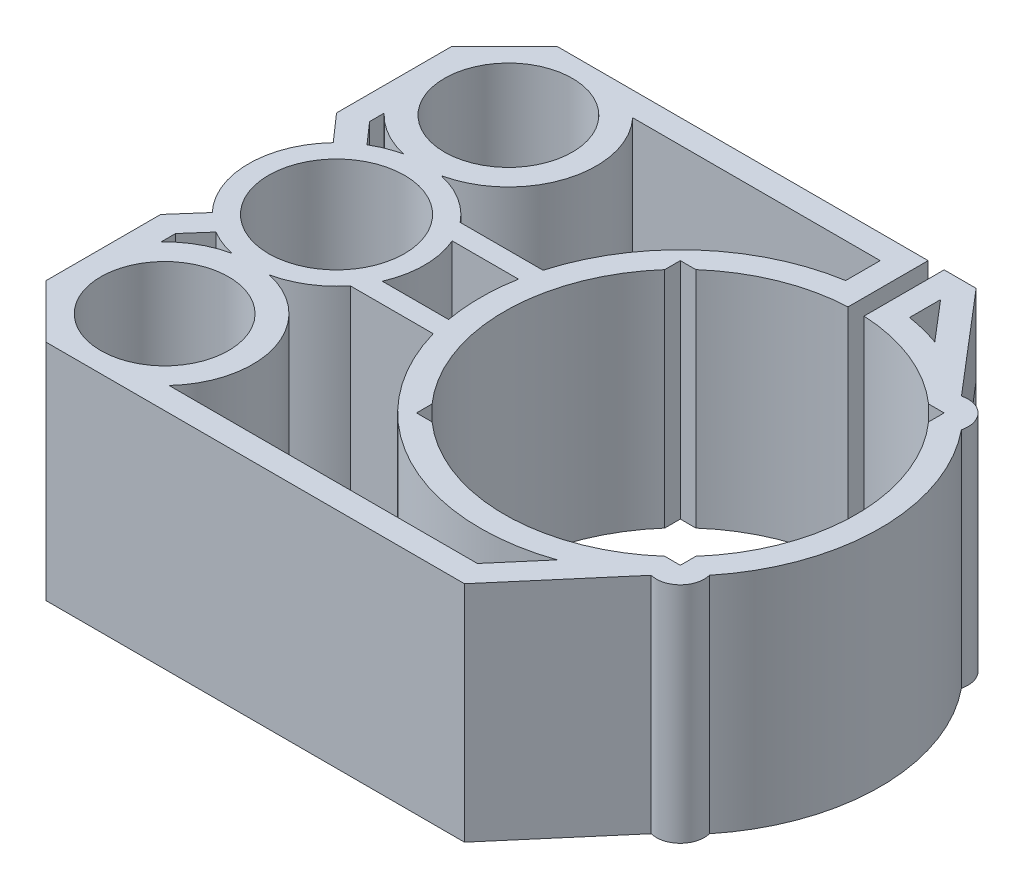
SolidWorks part; units mm, degrees
ref_plane "Front Plane" through (0, 0, 0) normal (0, 0, 1) x (1, 0, 0)
ref_plane "Top Plane" through (0, 0, 0) normal (0, 1, 0) x (1, 0, 0)
ref_plane "Right Plane" through (0, 0, 0) normal (1, 0, 0) x (0, 0, -1)
sketch "Sketch1" plane through (0, 0, 0) normal (0, 1, 0) x (1, 0, 0)
  line L0 (0, 0) -> (0, 16.5) construction
  line L1 (0, 16.5) -> (16.5, 16.5) construction
  line L2 (16.5, 16.5) -> (-16.5, -16.5) construction
  line L3 (0, 22) -> (0, 32) construction
  line L4 (16.5, 16.5) -> (-16.5, 16.5)
  line L5 (16.5, 16.5) -> (16.5, -16.5)
  line L6 (16.5, -16.5) -> (-16.5, -16.5)
  line L7 (-16.5, 16.5) -> (-16.5, -16.5)
  line L8 (1, 22) -> (1, 32)
  line L9 (-1, 22) -> (-1, 32)
  line L10 (1, 32) -> (5, 32)
  line L11 (5, 32) -> (15.7595, 19.4072)
  line L12 (18.6213, 18.6213) -> (16.5, 16.5) construction
  line L13 (4, 21.6333) -> (4, 28.5521)
  line L14 (-34.9533, 29) -> (-23.2995, 29)
  line L15 (4, 28.5521) -> (13.6619, 17.2439)
  line L16 (5, -32) -> (15.7595, -19.4072)
  line L17 (0, 0) -> (0, -25) construction
  line L18 (0, -25) -> (0, -32) construction
  line L19 (0, -32) -> (5, -32)
  line L20 (0, -32) -> (-23.2995, -32)
  line L21 (-1, 32) -> (-23.2995, 32)
  line L22 (0, -29) -> (-23.2995, -29)
  line L23 (0, -29) -> (3.6179, -29)
  line L24 (3.6179, -29) -> (13.6638, -17.2424)
  line L25 (-4, 22) -> (-4, 29)
  line L26 (-4, 29) -> (-23.2995, 29)
  line L27 (-23.2995, 32) -> (-23.2995, 29)
  line L28 (-23.2995, -29) -> (-23.2995, -32)
  line L29 (0, -29) -> (0, -25)
  line L30 (-3, -29) -> (-3, -24.8193)
  line L31 (1, 22) -> (1, 21.9773)
  line L32 (-1, 22) -> (-1, 21.9773)
  line L33 (-23.2995, -32) -> (-47.3408, -32)
  line L34 (-47.3408, -32) -> (-54, -25.3408)
  line L35 (-54, -25.3408) -> (-54, -11)
  line L36 (-54, -11) -> (-43, 0) construction
  line L37 (0, 0) -> (-43, 0) construction
  line L38 (-43, -32) -> (-43, 0) construction
  line L39 (-43, -21.5) -> (-54, -21.5) construction
  line L40 (-43, -21.5) -> (-50.6704, -28.6704) construction
  line L41 (-50.9825, -7.5683) -> (-54, -11)
  line L42 (-16.5, -29) -> (-16.5, -18.7816)
  line L43 (-19, -29) -> (-19, -16.2481)
  line L44 (-23.2995, -29) -> (-34.9533, -29)
  line L45 (-48.6381, -9.4452) -> (-51, -12.1314)
  line L46 (-51, -12.1314) -> (-51, -13.9502)
  line L47 (-24.0375, -6.8703) -> (-34.4094, -6.8703)
  line L48 (-32.9054, -4.3703) -> (-24.615, -4.3703)
  line L49 (-23.2995, 32) -> (-47.3408, 32)
  line L50 (-32.9054, 4.3703) -> (-24.615, 4.3703)
  line L51 (-50.9825, 7.5683) -> (-54, 11)
  line L52 (-48.6381, 9.4452) -> (-51, 12.1314)
  line L53 (-51, 12.1314) -> (-51, 13.9502)
  line L54 (-54, 25.3408) -> (-54, 11)
  line L55 (-47.3408, 32) -> (-54, 25.3408)
  line L56 (15.6445, -19.5504) -> (5, -32) construction
  line L57 (13.3643, -17.6008) -> (3.6179, -29) construction
  line L58 (-24.0375, 6.8703) -> (-34.4094, 6.8703)
  circle A0 centre (0, 0) radius 25
  circle A1 centre (0, 0) radius 22
  arc A2 (15.7595, -19.4072) -> (19.4072, -15.7595) centre (16.5, -16.5) ccw
  arc A3 (15.7595, 19.4072) -> (19.4072, 15.7595) centre (16.5, 16.5) cw
  arc A5 (-34.9533, -29) -> (-54, -21.5) centre (-43, -21.5) ccw
  circle A6 centre (-43, -21.5) radius 8
  circle A7 centre (-43, 0) radius 8.5
  circle A8 centre (-43, 0) radius 11
  arc A11 (-34.9533, 29) -> (-54, 21.5) centre (-43, 21.5) cw
  circle A12 centre (-43, 21.5) radius 8
  point P24 (0, 0)
  point P58 (-43, -29.5)
  point P60 (-51, -21.5)
  point P61 (-48.8441, -26.9632)
  point P69 (-16.5, -23.8908)
  point P73 (-43, -13.5)
  point P75 (-43, -8.5)
  point P76 (0, -22)
  point P77 (-35, -21.5)
  point P80 (-32.9054, -4.3703)
  point P81 (-24.615, -4.3703)
  dimension "D1" = 50
  dimension "D6" = 3
  dimension "D17" = 17
  dimension "D18" = 16
  dimension "D24" = 2.5
  dimension "D26" = 3
  dimension "D29" = 37.5
  dimension "D12" = 3
  dimension "D3" = 16.5
  dimension "D4" = 16.5
  dimension "D5" = 46.669
  dimension "D8" = 10
  dimension "D11" = 4
  dimension "D13" = 10
  dimension "D16" = 3
  dimension "D19" = 2.5
  dimension "D20" = 3
  dimension "D21" = 135
  dimension "D22" = 2.5
  dimension "D23" = 45
  dimension "D25" = 2.5
  dimension "D27" = 3
  dimension "D28" = 3
  dimension "D30" = 2.5
  dimension "D7" = 3
  dimension "D2" = 3
  dimension "D9" = 1
  dimension "D10" = 1
  dimension "D14" = 3
  dimension "D15" = 3
extrude "Boss-Extrude1" add sketch "Sketch1" along normal blind 28 contours A0 L11 L10 L8 L13 L15 | A1 L13 A0 L8 L31 | A1 L15 A0 L13 | A1 L5 L6 L24 A0 L15 L4 | A1 L32 L9 A0 L24 L6 L7 L4 | A3 A0 | A0 A2 | A0 L24 L23 L22 L28 L20 L19 L16 | A8 L47 A0 L48 | A8 A5 L35 L34 L33 L28 L44 A6 | A0 L9 L21 L27 L26 L25 | A5 A8 | A8 A11 A5 A7 | A11 A8 L14 L27 L49 L55 L54 A12 | A11 A8 | A8 L50 A0 L58 | A8 L41 L35 A5 L46 L45 | L53 A11 L54 L51 A8 L52 region at (15.5258, 0, -17.0011) region at (-15.5258, 0, -17.1319) region at (7.5368, 0, -21.8891) region at (5.9588, 0, -27.1719) region at (2.5035, 0, -23.3494) region at (18.045, 0, -18.045) region at (-10.6415, 0, -29.9407) region at (-4.4132, 0, 29.2881) region at (18.045, 0, 18.045) region at (-23.6729, 0, -30.5) region at (-28.9739, 0, -5.6671) region at (-33.8377, 0, -5.5118) region at (-43, 0, -10.75) region at (-28.9739, 0, 5.6671) region at (-35.3202, 0, 31.6266) region at (-52.1214, 0, -12.3199) region at (-43, 0, 10.75) region at (-52.1214, 0, 12.3199)
ref_plane "Plane1" through (19.4072, 0, 0) normal (-1, 0, 0) x (0, 0, 1)
sketch "Sketch4" plane through (4, 0, 0) normal (1, 0, 0) x (0, 0, -1)
  line L4 (24.6779, 0) -> (28.5521, 0)
  line L5 (24.6779, 20) -> (28.5521, 20)
  line L6 (24.6779, 20) -> (24.6779, 8)
  line L7 (24.6779, 8) -> (28.5521, 8)
  line L8 (24.6779, 0) -> (28.5521, 0)
  line L9 (28.5521, 0) -> (28.5521, 28)
  line L10 (28.5521, 28) -> (24.6779, 28)
  line L11 (24.6779, 28) -> (24.6779, 0)
  line L12 (28.5521, 28) -> (24.6779, 28)
  line L13 (28.5521, 0) -> (28.5521, 28) construction
  line L15 (24.6779, 28) -> (24.6779, 0) construction
  line L16 (28.5521, 20) -> (28.5521, 8)
  point P6 (24.6779, 14)
  dimension "D2" = 12
  dimension "D1" = 0
ref_plane "Plane2" through (0, 20, 0) normal (0, -1, 0) x (0, 0, -1)
ref_plane "Plane3" through (0, 8, 0) normal (0, -1, 0) x (0, 0, -1)
sketch "Sketch6" plane through (0, 20, 0) normal (0, -1, 0) x (0, 0, -1)
  line L0 (30.7174, 3.9637) -> (22.7854, 3.9637)
  line L1 (22.7854, 3.9637) -> (22.7854, 10.6041)
  line L2 (22.7854, 10.6041) -> (30.7174, 3.9637)
extrude "Boss-Extrude3" add sketch "Sketch6" along normal up to surface (12 mm away) up to plane "Plane3"
sketch "Sketch3" plane through (19.4072, 0, 0) normal (-1, 0, 0) x (0, 0, 1)
  line L0 (-32, 14) -> (-27, 14) construction
  line L1 (-32, 28) -> (-32, 0) construction
  line L2 (-27, 14) -> (-27, 10) construction
  line L3 (-32, 14) -> (-32, 18) construction
  line L5 (-32, 18) -> (-27, 18)
  line L6 (-32, 18) -> (-32, 10)
  line L7 (-32, 10) -> (-27, 10)
  line L8 (-27, 18) -> (-27, 10)
  circle A0 centre (-27, 14) radius 4
  dimension "D1" = 5
  dimension "D2" = 4
  dimension "D3" = 4
extrude "Cut-Extrude1" cut sketch "Sketch3" along normal up to vertex (14.4072 mm away) contours L8 A0 | L8 A0 | A0 L5 L6 L7 region at (19.4072, 17.9057, -29.5) region at (19.4072, 14, -25.3023) region at (19.4072, 14, -28.6977) up to point (5, 28, -32)
sketch "Sketch7" plane through (0, 0, 0) normal (0, -1, 0) x (1, 0, 0)
  line L0 (-43, 0) -> (-48.646, -5.6677) construction
  circle A0 centre (-43, 0) radius 5
  circle A1 centre (-43, 0) radius 6.165
  circle A2 centre (-43, 0) radius 8.5
  circle A3 centre (-43, 0) radius 8
  circle A4 centre (-48.646, -5.6677) radius 1.425
  circle A5 centre (-48.6569, 5.6569) radius 1.425
  circle A6 centre (-37.3323, 5.6677) radius 1.425
  circle A7 centre (-37.3215, -5.6568) radius 1.425
  point P17 (-42.9892, 0)
  dimension "D1" = 10
  dimension "D2" = 12.33
  dimension "D3" = 16
  dimension "D4" = 2.85
  dimension "D5" = 4
extrude "Boss-Extrude4" add sketch "Sketch7" against normal blind 15 contours A2
extrude "Cut-Extrude2" cut sketch "Sketch7<3>" against normal blind 15 contours A0
sketch "Sketch7<3>" plane through (0, 0, 0) normal (0, -1, 0) x (1, 0, 0) same geometry as "Sketch7"
extrude "Cut-Extrude3" cut sketch "Sketch7<4>" against normal blind 1.5 contours A1
sketch "Sketch7<4>" plane through (0, 0, 0) normal (0, -1, 0) x (1, 0, 0) same geometry as "Sketch7"
extrude "Cut-Extrude4" cut sketch "Sketch7<5>" against normal blind 8 contours A4 | A5 | A6 | A7
sketch "Sketch7<5>" plane through (0, 0, 0) normal (0, -1, 0) x (1, 0, 0) same geometry as "Sketch7"
